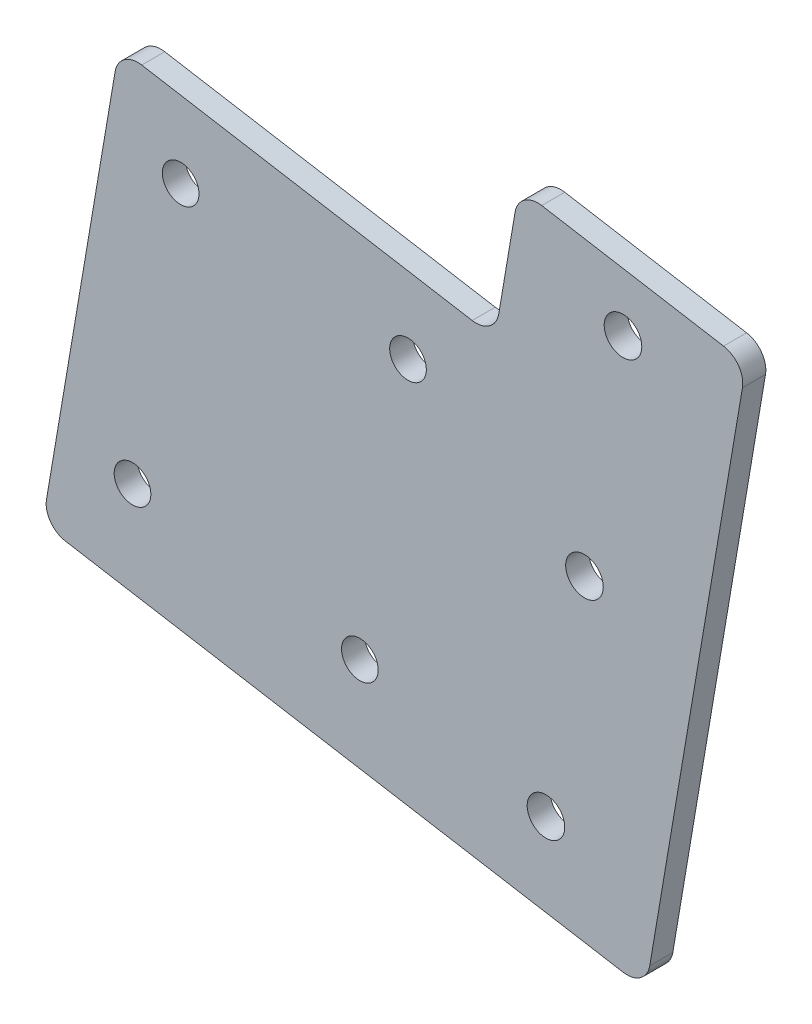
SolidWorks part; units mm, degrees
ref_plane "Front" through (0, 0, 0) normal (0, 0, 1) x (1, 0, 0)
ref_plane "Top" through (0, 0, 0) normal (0, 1, 0) x (1, 0, 0)
ref_plane "Right" through (0, 0, 0) normal (1, 0, 0) x (0, 0, -1)
sketch "Sketch1" plane through (0, 0, 0) normal (0, 0, 1) x (1, 0, 0)
  line L0 (-12.9599, -36.9844) -> (28.4499, -44.0009)
  line L1 (45.0856, -97.862) -> (56.1437, -32.5999)
  line L2 (45.0856, -97.862) -> (-21.3672, -86.6022)
  line L3 (-21.3672, -86.6022) -> (-12.9599, -36.9844)
  line L4 (56.1437, -32.5999) -> (31.1006, -28.3566)
  line L6 (-13.4611, -39.9422) -> (-15.0523, -49.3334) construction
  line L8 (20.0426, -93.6187) -> (-21.3672, -86.6022) construction
  line L10 (69.9345, 48.79) -> (44.4746, -101.4682) construction
  line L16 (28.4499, -44.0009) -> (31.1006, -28.3566)
  line L18 (35.9804, 0.4429) -> (32.5858, -19.5915) construction
  line L20 (20.5623, -42.6644) -> (-11.974, -37.1514) construction
  circle A0 centre (-6.1631, -46.5543) radius 2.0193
  circle A1 centre (-11.4673, -77.8581) radius 2.0193
  circle A2 centre (18.8799, -50.7977) radius 2.0193
  circle A3 centre (13.5758, -82.1015) radius 2.0193
  circle A4 centre (38.318, -61.7821) radius 2.0701
  circle A5 centre (34.0747, -86.8251) radius 2.0701
  circle A6 centre (42.5613, -36.739) radius 2.0701
  arc A7 (42.8318, -34.6867) -> (42.1406, -38.7659) centre (42.5613, -36.739) ccw construction
  arc A9 (38.5885, -59.7297) -> (37.8973, -63.809) centre (38.318, -61.7821) ccw construction
  arc A10 (34.3452, -84.7727) -> (33.654, -88.852) centre (34.0747, -86.8251) ccw construction
  circle A11 centre (13.5758, -82.1015) radius 2.0193 construction
  circle A12 centre (18.8799, -50.7977) radius 2.0193 construction
  circle A13 centre (-6.1631, -46.5543) radius 2.0193 construction
  circle A14 centre (-11.4673, -77.8581) radius 2.0193 construction
  point P0 (0, 0)
  dimension "D2" = 6.35
extrude "Boss-Extrude1" add sketch "Sketch1" along normal blind 2.54
fillet "Fillet2" radius 2.54 6 edges at (28.4499, -44.0009, 1.27) (31.1006, -28.3566, 1.27) (56.1437, -32.5999, 1.27) (45.0856, -97.862, 1.27) (-21.3672, -86.6022, 1.27) (-12.9599, -36.9844, 1.27)
